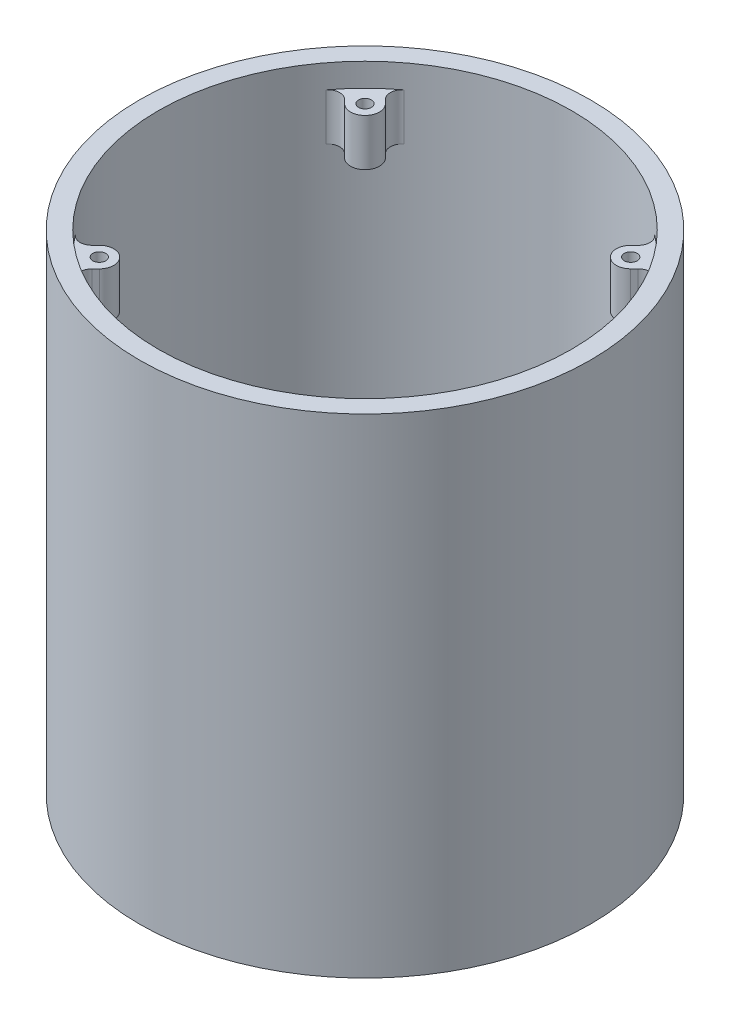
SolidWorks part; units mm, degrees
ref_plane "Front Plane" through (0, 0, 0) normal (0, 0, 1) x (1, 0, 0)
ref_plane "Top Plane" through (0, 0, 0) normal (0, 1, 0) x (1, 0, 0)
ref_plane "Right Plane" through (0, 0, 0) normal (1, 0, 0) x (0, 0, -1)
sketch "Sketch1" plane through (0, 872.6882, 0) normal (0, -1, 0) x (1, 0, 0)
  circle A0 centre (738.2581, 1221.2145) radius 88
  circle A1 centre (738.2581, 1221.2145) radius 87.5 construction
  circle A2 centre (738.2581, 1221.2145) radius 96
  dimension "D1" = 0.5
  dimension "D2" = 8
extrude "Boss-Extrude3" add sketch "Sketch1" against normal blind 208
sketch "Sketch2" plane through (0, 882.6882, 0) normal (0, 1, 0) x (1, 0, 0)
  line L0 (658.2581, -1213.7145) -> (650.5782, -1213.7145)
  line L1 (658.2581, -1228.7145) -> (650.5782, -1228.7145)
  line L2 (730.7581, -1301.2145) -> (730.7581, -1308.8943)
  line L3 (745.7581, -1301.2145) -> (745.7581, -1308.8943)
  line L4 (818.2581, -1228.7145) -> (825.9379, -1228.7145)
  line L5 (818.2581, -1213.7145) -> (825.9379, -1213.7145)
  line L6 (730.7581, -1141.2145) -> (730.7581, -1133.5347)
  line L7 (745.7581, -1141.2145) -> (745.7581, -1133.5347)
  arc A0 (658.2581, -1228.7145) -> (658.2581, -1213.7145) centre (658.2581, -1221.2145) ccw
  arc A1 (730.7581, -1141.2145) -> (745.7581, -1141.2145) centre (738.2581, -1141.2145) ccw
  arc A2 (818.2581, -1213.7145) -> (818.2581, -1228.7145) centre (818.2581, -1221.2145) ccw
  arc A3 (745.7581, -1301.2145) -> (730.7581, -1301.2145) centre (738.2581, -1301.2145) ccw
  circle A5 centre (738.2581, -1221.2145) radius 88 construction
  arc A6 (650.5782, -1213.7145) -> (650.5782, -1228.7145) centre (738.2581, -1221.2145) ccw
  arc A7 (730.7581, -1308.8943) -> (745.7581, -1308.8943) centre (738.2581, -1221.2145) ccw
  arc A8 (825.9379, -1228.7145) -> (825.9379, -1213.7145) centre (738.2581, -1221.2145) ccw
  arc A9 (745.7581, -1133.5347) -> (730.7581, -1133.5347) centre (738.2581, -1221.2145) ccw
  dimension "D1" = 15
extrude "Boss-Extrude4" add sketch "Sketch2" along normal blind 60 separate body
combine bodies "Combine1" operation type add bodies to combine 105 106 107 104 103
fillet "Fillet1" radius 8 8 edges at (745.7581, 912.6882, 1308.8943) (730.7581, 912.6882, 1308.8943) (650.5782, 912.6882, 1213.7145) (650.5782, 912.6882, 1228.7145) (825.9379, 912.6882, 1213.7145) (825.9379, 912.6882, 1228.7145) (745.7581, 912.6882, 1133.5347) (730.7581, 912.6882, 1133.5347)
sketch "Sketch3" plane through (0, 882.6882, 0) normal (0, -1, 0) x (1, 0, 0)
  circle A0 centre (738.2581, 1141.2145) radius 2.75 construction
  circle A1 centre (818.2581, 1221.2145) radius 2.75 construction
  circle A2 centre (738.2581, 1301.2145) radius 2.75 construction
  circle A3 centre (658.2581, 1221.2145) radius 2.75 construction
  circle A12 centre (738.2581, 1141.2145) radius 2.75
  circle A13 centre (818.2581, 1221.2145) radius 2.75
  circle A14 centre (738.2581, 1301.2145) radius 2.75
  circle A15 centre (658.2581, 1221.2145) radius 2.75
extrude "Cut-Extrude1" cut sketch "Sketch3" against normal blind 65
ref_plane "Plane1" through (0, 1070.6882, 0) normal (0, 1, 0) x (1, 0, 0)
sketch "Sketch5" plane through (0, 1070.6882, 0) normal (0, 1, 0) x (1, 0, 0)
  line L0 (677.3443, -1168.9911) -> (671.8394, -1163.4861)
  line L3 (686.0347, -1160.3008) -> (680.5297, -1154.7958)
  line L10 (0, -55) -> (0, 55) construction
  line L11 (677.3443, -1273.4378) -> (671.8394, -1278.9428)
  line L12 (686.0347, -1282.1282) -> (680.5297, -1287.6331)
  line L13 (790.4991, -1282.1105) -> (796.0053, -1287.6167)
  line L14 (799.1541, -1273.4555) -> (804.6603, -1278.9617)
  line L15 (790.4991, -1160.3184) -> (796.0053, -1154.8122)
  line L16 (799.1541, -1168.9734) -> (804.6603, -1163.4672)
  circle A2 centre (738.2581, -1221.2145) radius 88 construction
  arc A3 (796.0053, -1287.6167) -> (804.6603, -1278.9617) centre (738.2581, -1221.2145) ccw
  circle A8 centre (681.6895, -1277.783) radius 6.145 construction
  circle A11 centre (681.6895, -1277.783) radius 2.75 construction
  circle A16 centre (794.8266, -1277.783) radius 6.12 construction
  circle A21 centre (794.8266, -1277.783) radius 2.75 construction
  circle A22 centre (794.8266, -1164.6459) radius 2.75 construction
  circle A23 centre (794.8266, -1164.6459) radius 6.12 construction
  circle A24 centre (681.6895, -1164.6459) radius 6.145 construction
  circle A25 centre (681.6895, -1164.6459) radius 2.75 construction
  arc A26 (686.0347, -1282.1282) -> (677.3443, -1273.4378) centre (681.6895, -1277.783) ccw
  circle A27 centre (681.6895, -1277.783) radius 2.75
  arc A28 (799.1541, -1273.4555) -> (790.4991, -1282.1105) centre (794.8266, -1277.783) ccw
  circle A29 centre (794.8266, -1277.783) radius 2.75
  circle A30 centre (794.8266, -1164.6459) radius 2.75
  arc A31 (790.4991, -1160.3184) -> (799.1541, -1168.9734) centre (794.8266, -1164.6459) ccw
  arc A32 (677.3443, -1168.9911) -> (686.0347, -1160.3008) centre (681.6895, -1164.6459) ccw
  circle A33 centre (681.6895, -1164.6459) radius 2.75
  arc A34 (671.8394, -1278.9428) -> (680.5297, -1287.6331) centre (738.2581, -1221.2145) ccw
  arc A35 (680.5297, -1154.7958) -> (671.8394, -1163.4861) centre (738.2581, -1221.2145) ccw
  arc A36 (804.6603, -1163.4672) -> (796.0053, -1154.8122) centre (738.2581, -1221.2145) ccw
  dimension "D1" = 45
  dimension "D2" = 45
extrude "Boss-Extrude5" add sketch "Sketch5" against normal blind 20
fillet "Fillet3" radius 5 8 edges at (671.8394, 1060.6882, 1278.9428) (680.5297, 1060.6882, 1287.6331) (804.6603, 1060.6882, 1278.9617) (796.0053, 1060.6882, 1287.6167) (796.0053, 1060.6882, 1154.8122) (804.6603, 1060.6882, 1163.4672) (680.5297, 1060.6882, 1154.7958) (671.8394, 1060.6882, 1163.4861)
